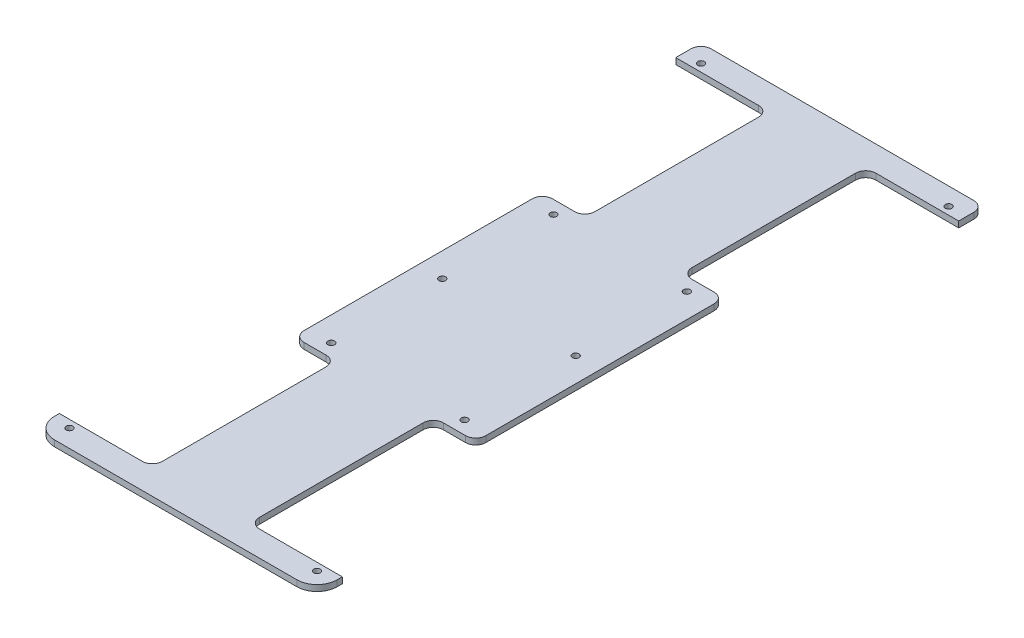
SolidWorks part; units mm, degrees
ref_plane "Front Plane" through (0, 0, 0) normal (0, 0, 1) x (1, 0, 0)
ref_plane "Top Plane" through (0, 0, 0) normal (0, 1, 0) x (1, 0, 0)
ref_plane "Right Plane" through (0, 0, 0) normal (1, 0, 0) x (0, 0, -1)
sketch "Sketch1" plane through (0, 0, 0) normal (0, 1, 0) x (1, 0, 0)
  line L0 (0, 0) -> (140, 0)
  line L1 (0, 0) -> (140, 0) construction
  line L2 (0, 0) -> (0, 330) construction
  line L3 (0, 330) -> (140, 330) construction
  line L4 (140, 0) -> (140, 330) construction
  line L5 (140, 0) -> (140, 12.5)
  line L6 (140, 12.5) -> (94, 12.5)
  line L7 (94, 12.5) -> (94, 103.5)
  line L11 (94, 226.5) -> (94, 317.5)
  line L12 (94, 317.5) -> (140, 317.5)
  line L13 (140, 317.5) -> (140, 330)
  line L14 (140, 330) -> (0, 330)
  line L15 (0, 330) -> (0, 317.5)
  line L16 (0, 317.5) -> (46, 317.5)
  line L17 (46, 317.5) -> (46, 226.5)
  line L21 (46, 103.5) -> (46, 12.5)
  line L22 (46, 12.5) -> (0, 12.5)
  line L23 (0, 12.5) -> (0, 0)
  line L24 (46, 226.5) -> (25, 226.5)
  line L25 (25, 226.5) -> (25, 103.5)
  line L26 (25, 103.5) -> (46, 103.5)
  line L27 (94, 226.5) -> (115, 226.5)
  line L28 (115, 226.5) -> (115, 103.5)
  line L29 (115, 103.5) -> (94, 103.5)
  dimension "D1" = 140
  dimension "D2" = 330
  dimension "D3" = 46
  dimension "D4" = 91
  dimension "D5" = 25
  dimension "D6" = 123
extrude "Boss-Extrude1" add sketch "Sketch1" along normal blind 3
fillet "Fillet1" radius 10 2 edges at (140, 1.5, 0) (0, 1.5, 0)
fillet "Fillet2" radius 5 6 edges at (0, 1.5, -330) (140, 1.5, -330) (115, 1.5, -226.5) (115, 1.5, -103.5) (25, 1.5, -103.5) (25, 1.5, -226.5)
sketch "Sketch2" plane through (0, 3, 0) normal (0, 1, 0) x (1, 0, 0)
  line L2 (37, 220) -> (37, 110) construction
  line L3 (25, 165) -> (37, 165) construction
  line L4 (25, 221.5) -> (25, 108.5) construction
  line L5 (70, 330) -> (70, 0) construction
  line L6 (135, 330) -> (5, 330) construction
  line L7 (10, 0) -> (130, 0) construction
  circle A0 centre (37, 220) radius 1.65
  circle A1 centre (37, 165) radius 1.65
  circle A2 centre (37, 110) radius 1.65
  circle A3 centre (103, 110) radius 1.65
  circle A4 centre (103, 165) radius 1.65
  circle A5 centre (103, 220) radius 1.65
  dimension "D3" = 3.3
  dimension "D1" = 12
  dimension "D2" = 110
extrude "Cut-Extrude1" cut sketch "Sketch2" against normal through all
sketch "Sketch3" plane through (0, 3, 0) normal (0, 1, 0) x (1, 0, 0)
  line L0 (0, 12.5) -> (8.75, 12.5) construction
  line L1 (46, 12.5) -> (0, 12.5) construction
  line L2 (8.75, 12.5) -> (8.75, 8.75) construction
  line L3 (70, 0) -> (70, 57.6288) construction
  line L4 (10, 0) -> (130, 0) construction
  circle A0 centre (8.75, 8.75) radius 1.65
  circle A1 centre (131.25, 8.75) radius 1.65
  dimension "D3" = 3.3
  dimension "D1" = 8.75
  dimension "D2" = 3.75
extrude "Cut-Extrude2" cut sketch "Sketch3" against normal through all
sketch "Sketch4" plane through (0, 3, 0) normal (0, 1, 0) x (1, 0, 0)
  line L0 (0, 317.5) -> (8.75, 317.5) construction
  line L1 (0, 317.5) -> (46, 317.5) construction
  line L2 (8.75, 317.5) -> (8.75, 321.25) construction
  line L3 (70, 330) -> (70, 288.2737) construction
  line L4 (135, 330) -> (5, 330) construction
  circle A0 centre (8.75, 321.25) radius 1.65
  circle A1 centre (131.25, 321.25) radius 1.65
  dimension "D3" = 3.3
  dimension "D1" = 8.75
  dimension "D2" = 3.75
extrude "Cut-Extrude3" cut sketch "Sketch4" against normal through all
fillet "Fillet3" radius 5 8 edges at (94, 1.5, -226.5) (46, 1.5, -226.5) (94, 1.5, -103.5) (46, 1.5, -103.5) (46, 1.5, -12.5) (94, 1.5, -12.5) (46, 1.5, -317.5) (94, 1.5, -317.5)
